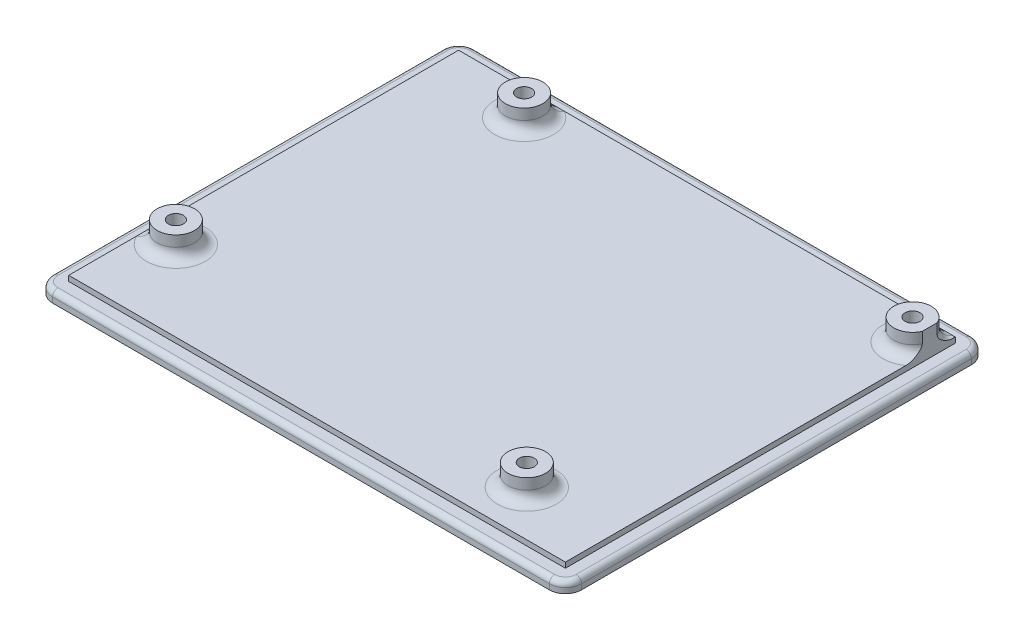
SolidWorks part; units mm, degrees
ref_plane "Спереди" through (0, 0, 0) normal (0, 0, 1) x (1, 0, 0)
ref_plane "Сверху" through (0, 0, 0) normal (0, 1, 0) x (1, 0, 0)
ref_plane "Справа" through (0, 0, 0) normal (1, 0, 0) x (0, 0, -1)
sketch "Эскиз1" plane through (0, 0, 0) normal (0, 1, 0) x (1, 0, 0)
  line L1 (0, 0) -> (92.71, 0)
  line L2 (0, 0) -> (0, 72.77)
  line L3 (0, 72.77) -> (92.71, 72.77)
  line L4 (92.71, 0) -> (92.71, 72.77)
  dimension "D1" = 92.71
  dimension "D2" = 72.77
extrude "Бобышка-Вытянуть1" add sketch "Эскиз1" along normal blind 3
sketch "Эскиз2" plane through (0, 3, 0) normal (0, 1, 0) x (1, 0, 0)
  line L0 (92.71, 66.605) -> (92.71, 69.395)
  line L4 (0, 72.77) -> (0, 0)
  line L5 (0, 0) -> (92.71, 0)
  line L6 (92.71, 0) -> (92.71, 72.77)
  line L7 (92.71, 72.77) -> (0, 72.77)
  line L8 (0, 72.77) -> (0, 0) construction
  line L9 (0, 0) -> (92.71, 0) construction
  line L10 (92.71, 0) -> (92.71, 69.395) construction
  line L11 (92.71, 72.77) -> (0, 72.77) construction
  circle A0 centre (89.5, 68) radius 1.1
  arc A1 (92.71, 69.395) -> (92.71, 66.605) centre (89.5, 68) ccw
  circle A2 centre (17, 68) radius 1.1
  circle A3 centre (17, 68) radius 3.5
  circle A4 centre (5, 15) radius 1.1
  circle A5 centre (5, 15) radius 3.5
  circle A6 centre (77, 8.5) radius 1.1
  circle A7 centre (77, 8.5) radius 3.5
  point P17 (92.71, 66.605)
  point P18 (92.71, 72.77)
  dimension "D2" = 2.2
  dimension "D3" = 2.2
  dimension "D4" = 2.2
  dimension "D5" = 2.2
  dimension "D6" = 7
  dimension "D7" = 7
  dimension "D8" = 7
  dimension "D9" = 7
  dimension "D10" = 8.5
  dimension "D11" = 68
  dimension "D12" = 89.5
  dimension "D13" = 17
  dimension "D14" = 4.77
  dimension "D15" = 5
  dimension "D16" = 15
  dimension "D17" = 72
  dimension "D1" = 0
extrude "Бобышка-Вытянуть2" add sketch "Эскиз2" along normal blind 4
sketch "Эскиз3" plane through (0, 7, 0) normal (0, 1, 0) x (1, 0, 0)
  circle A0 centre (17, 68) radius 1.4
  circle A1 centre (89.5, 68) radius 1.4
  circle A2 centre (77, 8.5) radius 1.4
  circle A3 centre (5, 15) radius 1.4
  dimension "D1" = 2.8
  dimension "D2" = 2.8
  dimension "D3" = 2.8
  dimension "D4" = 2.8
extrude "Вырез-Вытянуть1" cut sketch "Эскиз3" against normal blind 3
fillet "Скругление1" radius 2 4 edges at (5, 3, -18.5) (77, 3, -12) (86, 3, -68) (17, 3, -71.5)
sketch "Эскиз5" plane through (0, 3, 0) normal (0, 1, 0) x (1, 0, 0)
  circle A0 centre (77, 8.5) radius 1.1 construction
  circle A1 centre (5, 15) radius 1.1 construction
  circle A2 centre (17, 68) radius 1.1 construction
  circle A3 centre (89.5, 68) radius 1.1 construction
  circle A4 centre (77, 8.5) radius 1.1
  circle A5 centre (5, 15) radius 1.1
  circle A6 centre (17, 68) radius 1.1
  circle A7 centre (89.5, 68) radius 1.1
extrude "Вырез-Вытянуть2" cut sketch "Эскиз5" against normal blind 3
sketch "Эскиз6" plane through (0, 0, 0) normal (0, -1, 0) x (1, 0, 0)
  line L0 (0, -72.77) -> (0, 0) construction
  line L1 (-3, -75.77) -> (95.71, -75.77)
  line L2 (-3, -75.77) -> (-3, 3)
  line L3 (-3, 3) -> (95.71, 3)
  line L4 (95.71, -75.77) -> (95.71, 3)
  line L5 (92.71, 0) -> (92.71, -72.77) construction
  line L6 (92.71, -72.77) -> (0, -72.77) construction
  line L7 (0, 0) -> (92.71, 0) construction
  line L12 (0, 0) -> (0, -72.77)
  line L13 (0, -72.77) -> (92.71, -72.77)
  line L14 (92.71, -72.77) -> (92.71, 0)
  line L15 (92.71, 0) -> (0, 0)
  line L16 (0, 0) -> (0, -72.77)
  line L17 (0, -72.77) -> (92.71, -72.77)
  line L18 (92.71, -72.77) -> (92.71, 0)
  line L19 (92.71, 0) -> (0, 0)
  dimension "D1" = 3
  dimension "D2" = 3
  dimension "D3" = 3
  dimension "D4" = 3
  dimension "D5" = 0
extrude "Бобышка-Вытянуть3" add sketch "Эскиз6" against normal blind 2
fillet "Скругление2" radius 3 4 edges at (-3, 1, -75.77) (-3, 1, 3) (95.71, 1, 3) (95.71, 1, -75.77)
fillet "Скругление4" radius 1 8 edges at (94.8313, 2, 2.1213) (95.71, 2, -36.385) (94.8313, 2, -74.8913) (46.355, 2, -75.77) (-2.1213, 2, -74.8913) (-3, 2, -36.385) (-2.1213, 2, 2.1213) (46.355, 2, 3)
